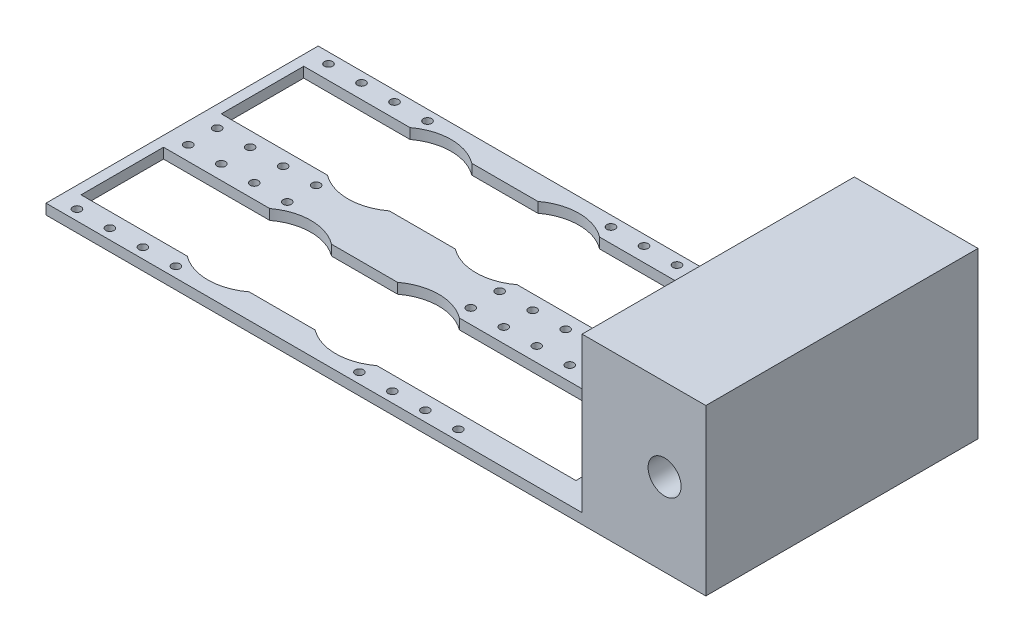
SolidWorks part; units mm, degrees
ref_plane "Front Plane" through (0, 0, 0) normal (0, 0, 1) x (1, 0, 0)
ref_plane "Top Plane" through (0, 0, 0) normal (0, 1, 0) x (1, 0, 0)
ref_plane "Right Plane" through (0, 0, 0) normal (1, 0, 0) x (0, 0, -1)
sketch "Sketch1" plane through (0, 0, 0) normal (0, 1, 0) x (1, 0, 0)
  line L1 (-80, 33) -> (80, 33)
  line L2 (-80, 33) -> (-80, -33)
  line L3 (-80, -33) -> (80, -33)
  line L4 (80, 33) -> (80, -33)
  line L5 (-80, 33) -> (80, -33) construction
  line L6 (-80, -33) -> (80, 33) construction
  point P0 (0, 0)
  dimension "D1" = 160
  dimension "D2" = 66
extrude "Boss-Extrude1" add sketch "Sketch1" along normal blind 40
sketch "Sketch2" plane through (0, 0, 33) normal (0, 0, 1) x (1, 0, 0)
  line L0 (80, 40) -> (80, 0) construction
  line L1 (-80, 40) -> (80, 40) construction
  line L2 (-80, 40) -> (50, 40)
  line L3 (-80, 40) -> (-80, 2.5)
  line L4 (-80, 2.5) -> (50, 2.5)
  line L5 (50, 40) -> (50, 2.5)
  line L6 (-80, 40) -> (50, 2.5) construction
  line L7 (-80, 2.5) -> (50, 40) construction
  line L8 (-80, 40) -> (-80, 0) construction
  circle A0 centre (70, 20) radius 4
  point P4 (80, 20)
  point P5 (-15, 21.25)
  dimension "D1" = 8
  dimension "D2" = 10
  dimension "D3" = 37.5
  dimension "D4" = 130
extrude "Cut-Extrude1" cut sketch "Sketch2" against normal through all
sketch "Sketch3" plane through (0, 40, 0) normal (0, 1, 0) x (1, 0, 0)
  line L0 (-80, 33) -> (-80, -33) construction
  line L1 (80, 33) -> (50, 33) construction
  line L2 (-75, 30.5) -> (-67, 30.5) construction
  line L3 (-75, 3.5) -> (-67, 3.5) construction
  line L4 (0, 0) -> (13.7346, 0) construction
  line L5 (-80, 33) -> (-80, -33) construction
  line L6 (-6.5, 30.5) -> (1.5, 30.5) construction
  line L7 (-75, 30.5) -> (-75, 3.5) construction
  line L8 (-77.5, 27) -> (42.5, 27)
  line L9 (-77.5, 27) -> (-77.5, 7)
  line L10 (-77.5, 7) -> (42.5, 7)
  line L11 (42.5, 27) -> (42.5, 7)
  line L12 (-6.5, 3.5) -> (1.5, 3.5) construction
  line L13 (-6.5, -3.5) -> (1.5, -3.5) construction
  line L14 (-75, -30.5) -> (-75, -3.5) construction
  line L15 (-6.5, -30.5) -> (1.5, -30.5) construction
  line L16 (-75, -3.5) -> (-67, -3.5) construction
  line L17 (-75, -30.5) -> (-67, -30.5) construction
  line L18 (42.5, -27) -> (42.5, -7)
  line L19 (-77.5, -7) -> (42.5, -7)
  line L20 (-77.5, -27) -> (-77.5, -7)
  line L21 (-77.5, -27) -> (42.5, -27)
  circle A0 centre (-75, 30.5) radius 1
  circle A1 centre (-75, 3.5) radius 1
  circle A2 centre (-67, 30.5) radius 1
  circle A3 centre (-59, 30.5) radius 1
  circle A4 centre (-51, 30.5) radius 1
  circle A11 centre (-67, 3.5) radius 1
  circle A12 centre (-59, 3.5) radius 1
  circle A13 centre (-51, 3.5) radius 1
  circle A50 centre (-6.5, 30.5) radius 1
  circle A51 centre (-6.5, 3.5) radius 1
  circle A52 centre (1.5, 30.5) radius 1
  circle A53 centre (9.5, 30.5) radius 1
  circle A54 centre (17.5, 30.5) radius 1
  circle A55 centre (1.5, 3.5) radius 1
  circle A56 centre (9.5, 3.5) radius 1
  circle A57 centre (17.5, 3.5) radius 1
  circle A58 centre (17.5, -3.5) radius 1
  circle A59 centre (9.5, -3.5) radius 1
  circle A60 centre (1.5, -3.5) radius 1
  circle A61 centre (17.5, -30.5) radius 1
  circle A62 centre (9.5, -30.5) radius 1
  circle A63 centre (1.5, -30.5) radius 1
  circle A64 centre (-6.5, -3.5) radius 1
  circle A65 centre (-6.5, -30.5) radius 1
  circle A66 centre (-51, -3.5) radius 1
  circle A67 centre (-59, -3.5) radius 1
  circle A68 centre (-67, -3.5) radius 1
  circle A69 centre (-51, -30.5) radius 1
  circle A70 centre (-59, -30.5) radius 1
  circle A71 centre (-67, -30.5) radius 1
  circle A72 centre (-75, -3.5) radius 1
  circle A73 centre (-75, -30.5) radius 1
  point P96 (-77.5, 17)
  point P97 (-75, 17)
  dimension "D1" = 2
  dimension "D3" = 2.5
  dimension "D4" = 27
  dimension "D12" = 2
  dimension "D2" = 5
  dimension "D6" = 8
  dimension "D8" = 8
  dimension "D9" = 20
  dimension "D10" = 120
  dimension "D11" = 2.5
  dimension "D13" = 44.5
  dimension "D15" = 8
  dimension "D17" = 8
  dimension "D5" = 4
  dimension "D7" = 4
  dimension "D14" = 4
  dimension "D16" = 4
extrude "Cut-Extrude2" cut sketch "Sketch3" against normal through all
sketch "Sketch4" plane through (0, 2.5, 0) normal (0, 1, 0) x (1, 0, 0)
  line L1 (-77.5, -7) -> (42.5, -7) construction
  line L2 (-77.5, 27) -> (42.5, 27) construction
  circle A0 centre (-44.25, -17) radius 12.5
  circle A1 centre (-51, -3.5) radius 1 construction
  circle A2 centre (-44.25, 17) radius 12.5
  circle A3 centre (-13.25, 17) radius 12.5
  circle A4 centre (-13.25, -17) radius 12.5
  circle A5 centre (-6.5, -3.5) radius 1 construction
  dimension "D1" = 25
  dimension "D4" = 6.75
  dimension "D2" = 6.75
  dimension "D3" = 10
  dimension "D5" = 10
extrude "Cut-Extrude3" cut sketch "Sketch4" against normal through all
